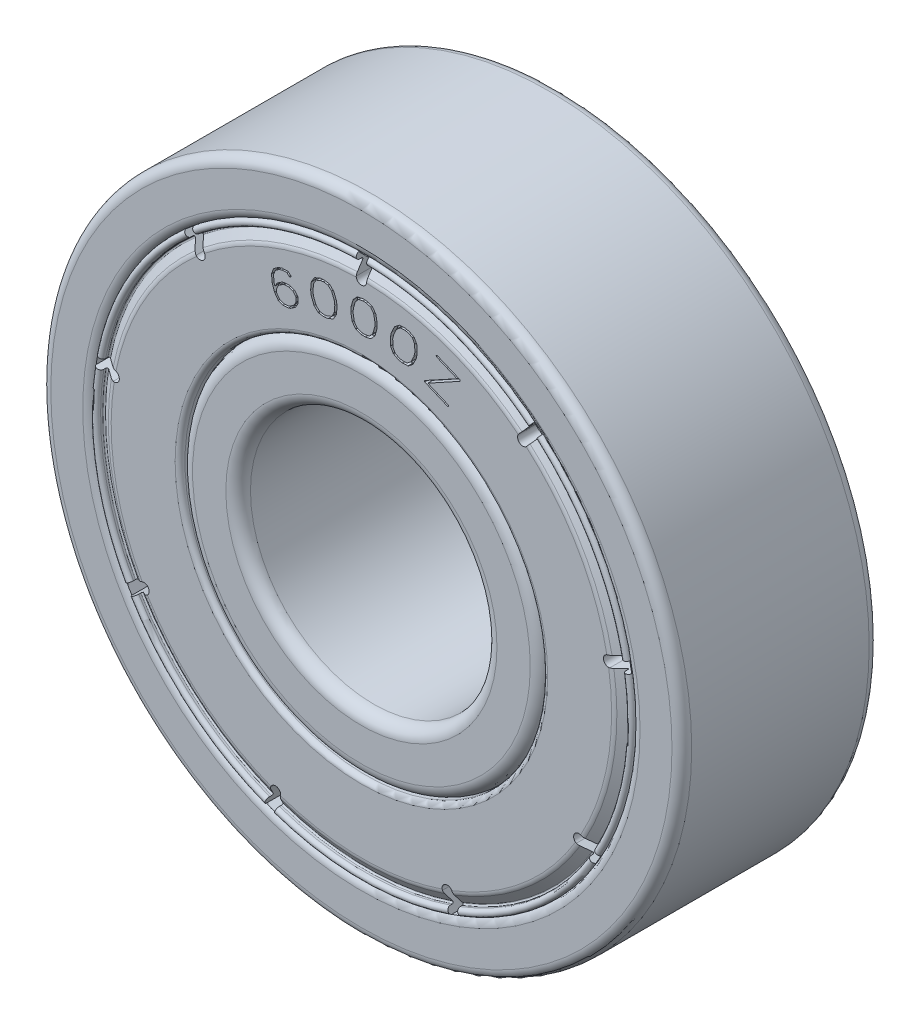
SolidWorks part; units mm, degrees
other "OD"
other "ID"
ref_plane "Front Plane" through (0, 0, 0) normal (0, 0, 1) x (1, 0, 0)
ref_plane "Top Plane" through (0, 0, 0) normal (0, 1, 0) x (1, 0, 0)
ref_plane "Right Plane" through (0, 0, 0) normal (1, 0, 0) x (0, 0, -1)
sketch "Sketch1" plane through (0, 0, 0) normal (0, 0, 1) x (1, 0, 0)
  circle A0 centre (0, 0) radius 13
  circle A1 centre (0, 0) radius 5
  circle A2 centre (0, 0) radius 7.35
  circle A3 centre (0, 0) radius 11
  dimension "D1" = 26
  dimension "D2" = 10
  dimension "D3" = 14.7
  dimension "D4" = 22
extrude "Rings" add sketch "Sketch1" against normal blind 8 contours A0 | A3 | A2 | A1
sketch "Sketch3" plane through (0, 0, 0) normal (0, 1, 0) x (1, 0, 0)
  line L0 (0, 0) -> (0, 8) construction
  line L1 (13, 8) -> (-13, 8) construction
ref_axis "Axis1" through (0, 0, -8) along (0, 0, 1)
fillet "Fillet2" radius 0.5 4 edges at (5, 0, -8) (7.35, 0, -8) (5, 0, 0) (7.35, 0, 0)
sketch "Sketch5" plane through (0, 0, 0) normal (0, 1, 0) x (1, 0, 0)
  line L0 (-13, 0) -> (13, 0) construction
  line L4 (7.5567, 0) -> (10.151, 0)
  line L5 (10.7201, 0.1407) -> (10.7201, 0.2218)
  line L7 (7.3567, 0.2) -> (7.3567, 4)
  line L8 (11, 0.1407) -> (11, 4)
  line L11 (10.6427, 0.2636) -> (10.3154, 0.0491)
  line L15 (7.3567, 4) -> (11, 4)
  arc A0 (11, 0.1407) -> (10.7201, 0.1407) centre (10.8601, 0.1407) cw
  arc A1 (7.3567, 0.2) -> (7.5567, 0) centre (7.5567, 0.2) ccw
  arc A2 (10.6427, 0.2636) -> (10.7201, 0.2218) centre (10.6701, 0.2218) cw
  arc A3 (10.151, 0) -> (10.3154, 0.0491) centre (10.151, 0.3) ccw
  point P16 (10.2405, 0)
  dimension "D1" = 0.2
  dimension "D2" = 0.05
  dimension "D3" = 4
  dimension "D4" = 0.3
revolve "Balls cover" add sketch "Sketch5" angle 360 about L0
ref_plane "Plane1" through (0, 0, -4) normal (0, 0, 1) x (1, 0, 0)
fillet "Fillet6" radius 0.4 4 edges at (11, 0, 0) (11, 0, -8) (13, 0, 0) (13, 0, -8)
mirror "Mirror12" about plane through (0, 0, -4) normal (0, 0, 1) of "Balls cover"
sketch "Sketch12" plane through (0, 0, 0) normal (0, 0, 1) x (1, 0, 0)
  line L0 (0, 11.1954) -> (0, 9.826) construction
  line L2 (0.2117, 10.9935) -> (0.2117, 10.1866)
  line L3 (-0.2117, 10.9935) -> (-0.2117, 10.1866)
  line L4 (-0.2117, 10.9935) -> (0.2117, 10.9935)
  arc A2 (-0.2117, 10.1866) -> (0.2117, 10.1866) centre (0, 10.1866) ccw
extrude "Slots" cut sketch "Sketch12" against normal through all contours L3 A2 L2 L4
pattern_circular "CirPattern6" count 9 over 360 of "Slots"
sketch "Sketch18" plane through (0, 0, 0) normal (0, 0, 1) x (1, 0, 0)
  arc A0 (-3.3727, 7.5839) -> (3.7653, 7.3968) centre (0, 0) cw construction
  text T0 "6000Z" font "SWSimp" height in points 5
extrude "Model No" cut sketch "Sketch18" against normal blind 0.2
